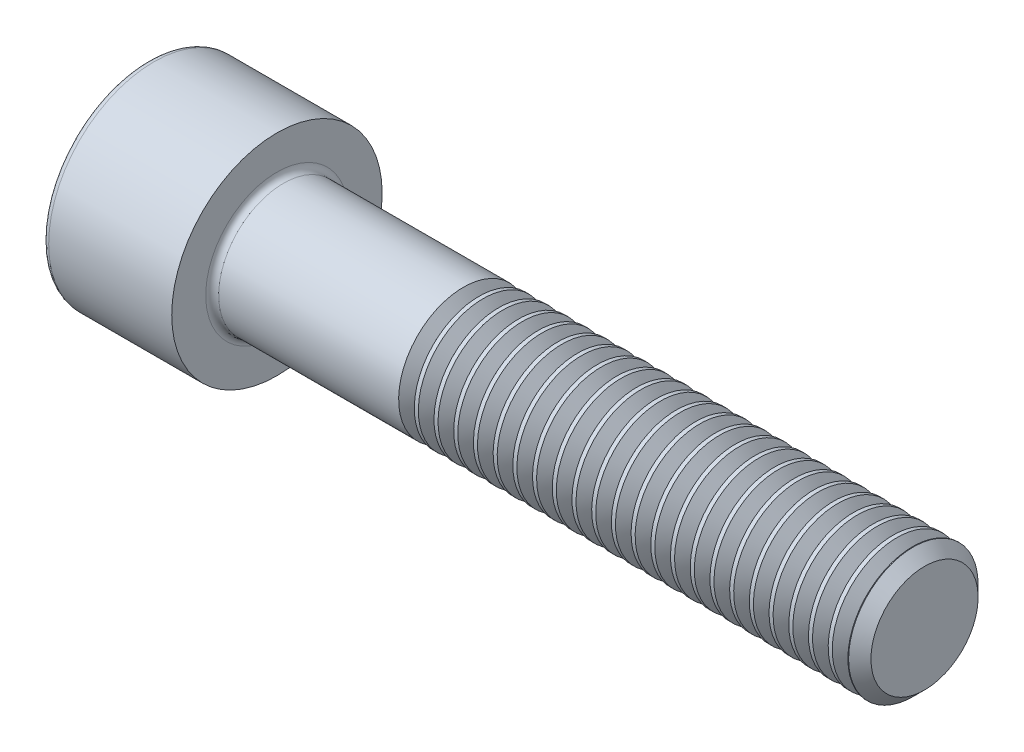
SolidWorks part; units mm, degrees
revolve "Base-Revolve" add sketch "BodySke"
sketch "BodySke" plane through (0, 0, 0) normal (0, 0, 1) x (1, 0, 0)
  line L0 (0, 0) -> (0, 6.5)
  line L1 (0, 6.5) -> (8, 6.5)
  line L2 (8, 6.5) -> (8, 4)
  line L3 (8, 4) -> (47.3095, 4)
  line L4 (48, 3.3095) -> (48, 0)
  line L5 (48, 0) -> (0, 0)
  line L6 (-31.75, 0) -> (127, 0) construction
  line L8 (48, 3.3095) -> (47.3095, 4)
  line L10 (48, -3.3095) -> (47.3095, -4) construction
  line L11 (9.25, 9.525) -> (9.25, 3.175) construction
  line L12 (20, 9.525) -> (20, 3.175) construction
  line L13 (-12, 9.525) -> (-12, 3.175) construction
  dimension "Diameter" = 8
  dimension "Head_dia" = 13
cosmetic thread "ThreadCosmetic" [suppressed]
fillet "Fillet1" radius 0.4 1 edges at (8, 0, 4)
fillet "Fillet2" radius 0.4 1 edges at (0, 0, 6.5)
ref_plane "Plane1" through (0, 0, 0) normal (0, 0, 1) x (1, 0, 0)
ref_plane "Plane2" through (0, 0, 0) normal (0, 1, 0) x (1, 0, 0)
ref_plane "Plane3" through (0, 0, 0) normal (1, 0, 0) x (0, 0, -1)
sketch "Sketch2" plane through (0, 0, 0) normal (0, 0, 1) x (1, 0, 0)
  line L0 (0, 3.0475) -> (4, 3.0475)
  line L1 (4, 3.0475) -> (5.7595, 0)
  line L2 (-31.75, 0) -> (127, 0) construction
  line L3 (5.7595, 0) -> (0, 0)
  line L4 (0, 0) -> (0, 3.0475)
  line L6 (0, 0) -> (47.625, 0) construction
  dimension "D1" = 3.0475
  dimension "D2" = 60
revolve "Hex-PreBroach" cut sketch "Sketch2" angle 360 about L6
sketch "Sketch3" plane through (0, 0, 0) normal (-1, 0, 0) x (0, 0.5, 0.866)
  line L0 (1.7595, 3.0475) -> (-1.7595, 3.0475)
  line L1 (-1.7595, 3.0475) -> (-3.5189, 0)
  line L2 (1.7595, 3.0475) -> (3.5189, 0)
  line L3 (1.7595, -3.0475) -> (3.5189, 0)
  line L4 (1.7595, -3.0475) -> (-1.7595, -3.0475)
  line L5 (-1.7595, -3.0475) -> (-3.5189, 0)
  dimension "D1" = 3.0475
  dimension "D2" = 3.0475
extrude "Hex" cut sketch "Sketch3" against normal blind 4
sketch "ThdSchSke" plane through (0, 0, 0) normal (0, 0, 1) x (1, 0, 0)
  line L0 (20, -3.3095) -> (19.5165, -4)
  line L1 (20, -3.3095) -> (20.4835, -4)
  line L2 (20.4835, -4) -> (20.4835, -5)
  line L3 (-3.175, 0) -> (5.1513, 0) construction
  line L4 (0, 6.1) -> (0, -6.1) construction
  line L5 (20.4835, -5) -> (19.5165, -5)
  line L6 (19.5165, -5) -> (19.5165, -4)
  dimension "Diameter" = 8
  dimension "Thread_minor" = 6.619
  dimension "Start" = 20
revolve "ThreadSchematic" cut sketch "ThdSchSke" angle 360 about L3
pattern_linear "ThdSchPat" count 24 spacing 1.2174 along (1, 0, 0) of "ThreadSchematic"
equation "\"D2@Sketch3\" = \"Hex_size@Sketch3\" / 2"
equation "\"D1@Sketch3\" = \"Hex_size@Sketch3\" / 2"
equation "\"D1@Sketch2\" = \"Hex_size@Sketch3\" / 2"
equation "\"Thread_minor@ThreadCosmetic\"  =  \"Minor_dia@BodySke\""
equation "\"Depth@Sketch2\" =  \"Key_eng@Hex\""
equation "\"Thread_length@ThreadCosmetic\" = ((sgn( (\"Length@BodySke\" - \"Advance@BodySke\" * 3.0) - \"Thread_nom@BodySke\" )-1)*( (\"Length@BodySke\" - \"Advance@BodySke\" * 3.0) - \"Thread_nom@BodySke\" ))/-2+ \"Thread_nom@BodySke\""
equation "\"Thread_minor@ThdSchSke\" = \"Minor_dia@BodySke\""
equation "\"Diameter@ThdSchSke\" = \"Diameter@BodySke\""
equation "\"Overcut@ThdSchSke\" = \"Diameter@BodySke\" * 1.25"
equation "\"Start@ThdSchSke\" = \"Head_ht@BodySke\" + \"Length@BodySke\" - \"Thread_length@ThreadCosmetic\"  '---Non-countersunk---"
equation "\"Num_threads@ThdSchPat\" = int( \"Thread_length@ThreadCosmetic\" / \"Advance@BodySke\" + 0.999 )  + 1"
equation "\"Advance@ThdSchPat\" = \"Thread_length@ThreadCosmetic\" /  (\"Num_threads@ThdSchPat\" - 1) 'relax it"
equation "\"Num_threads@ThdSchPat\" = \"Num_threads@ThdSchPat\" - sgn( \"Num_threads@ThdSchPat\" - 1) '---chamfered tips only---"
